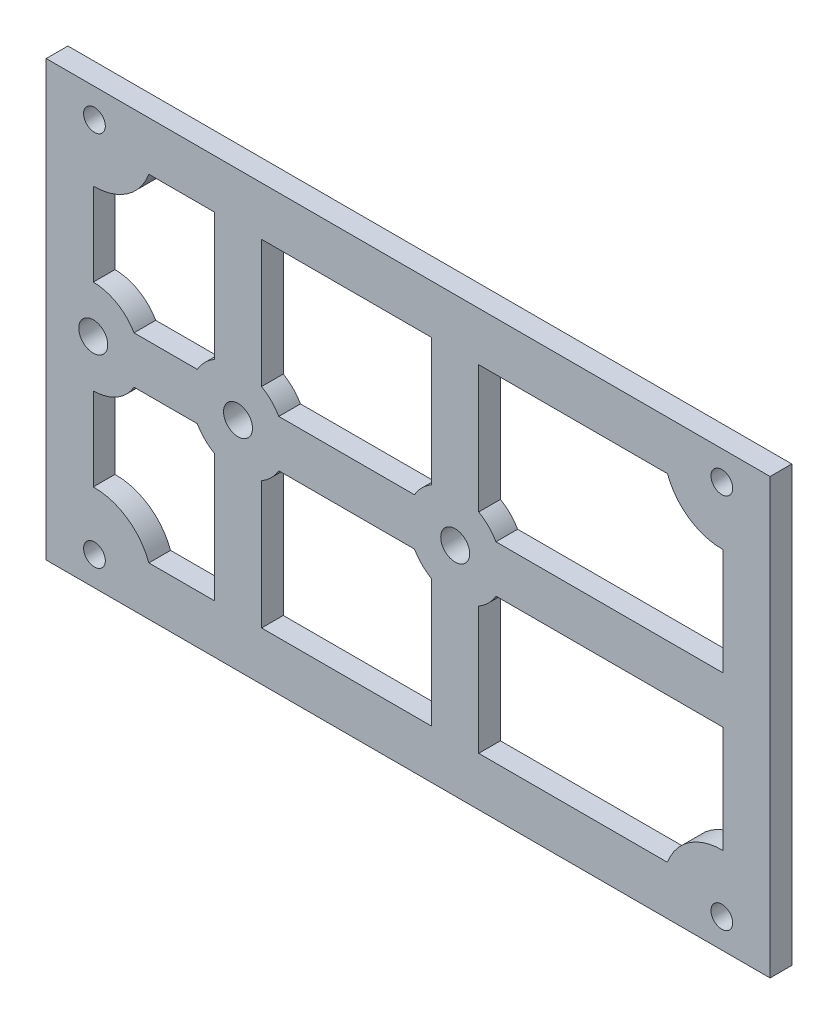
SolidWorks part; units mm, degrees
ref_plane "Front Plane" through (0, 0, 0) normal (0, 0, 1) x (1, 0, 0)
ref_plane "Top Plane" through (0, 0, 0) normal (0, 1, 0) x (1, 0, 0)
ref_plane "Right Plane" through (0, 0, 0) normal (1, 0, 0) x (0, 0, -1)
sketch "Sketch1" plane through (0, 0, 0) normal (0, 0, 1) x (1, 0, 0)
  line L1 (50, -30) -> (-50, -30)
  line L2 (50, -30) -> (50, 30)
  line L3 (50, 30) -> (-50, 30)
  line L4 (-50, -30) -> (-50, 30)
  line L5 (50, -30) -> (-50, 30) construction
  line L6 (50, 30) -> (-50, -30) construction
  point P0 (0, 0)
  dimension "D1" = 100
  dimension "D2" = 60
extrude "Boss-Extrude1" add sketch "Sketch1" along normal blind 3
sketch "Sketch3" plane through (0, 0, 0) normal (0, 0, -1) x (-1, 0, 0)
  line L0 (50, 0) -> (-6.5, 0) construction
  line L1 (50, 30) -> (50, -30) construction
  line L2 (50, -30) -> (50, 30) construction
  line L3 (-50, 30) -> (50, 30) construction
  line L4 (29.1292, 3.25) -> (37.8708, 3.25)
  line L5 (26.75, 5.6292) -> (26.75, 23.25)
  line L6 (26.75, 23.25) -> (35.8208, 23.25)
  line L7 (43.5, 6.5) -> (43.5, 18.0017)
  line L8 (-9.75, 23.25) -> (-35.8208, 23.25)
  line L9 (-9.75, 23.25) -> (-9.75, 5.6292)
  line L10 (-12.1292, 3.25) -> (-43.5, 3.25)
  line L11 (-43.5, 18.0017) -> (-43.5, 3.25)
  line L16 (-50, -30) -> (-50, 30) construction
  line L17 (-50, -30) -> (50, 30) construction
  line L18 (-50, 30) -> (50, -30) construction
  line L19 (-6.5, 0) -> (-50, 0) construction
  line L20 (-0.8708, 3.25) -> (17.8708, 3.25)
  line L21 (-3.25, 5.6292) -> (-3.25, 23.25)
  line L22 (-3.25, 23.25) -> (20.25, 23.25)
  line L23 (20.25, 5.6292) -> (20.25, 23.25)
  circle A1 centre (43.3333, 26) radius 1.5
  circle A2 centre (-43.3333, 26) radius 1.5
  circle A3 centre (23.5, 0) radius 2
  circle A4 centre (-6.5, 0) radius 2
  arc A6 (-43.5, 18.0017) -> (-35.8208, 23.25) centre (-43.3333, 26) ccw
  arc A7 (35.8208, 23.25) -> (43.5, 18.0017) centre (43.3333, 26) ccw
  arc A8 (-0.8708, 3.25) -> (-3.25, 5.6292) centre (-6.5, 0) ccw
  arc A9 (29.1292, 3.25) -> (26.75, 5.6292) centre (23.5, 0) ccw
  arc A10 (-9.75, 5.6292) -> (-12.1292, 3.25) centre (-6.5, 0) ccw
  arc A11 (43.5, 6.5) -> (37.8708, 3.25) centre (43.5, 0) ccw
  arc A12 (20.25, 5.6292) -> (17.8708, 3.25) centre (23.5, 0) ccw
  circle A13 centre (43.5, 0) radius 2
  dimension "D3" = 6.5
  dimension "D13" = 4
  dimension "D14" = 4
  dimension "D15" = 3
  dimension "D16" = 3
  dimension "D17" = 6.5
  dimension "D18" = 6.5
  dimension "D19" = 6.5
  dimension "D21" = 6.5
  dimension "D4" = 30
  dimension "D5" = 20
  dimension "D6" = 6.5
  dimension "D7" = 6.5
  dimension "D8" = 3.25
  dimension "D9" = 3.25
  dimension "D10" = 6.5
  dimension "D11" = 20
  dimension "D12" = 20
  dimension "D20" = 20
  dimension "D22" = 6.5
  dimension "D23" = 4
  dimension "D24" = 4
ref_plane "Plane1" through (50, -30, 0) normal (0, 1, 0) x (1, 0, 0)
sketch "Sketch4" plane through (0, 0, 0) normal (0, 0, 1) x (1, 0, 0)
extrude "Cut-Extrude2" cut sketch "Sketch3" against normal blind 10 contours A10 L9 L8 A6 L11 L10 | A9 L23 L22 L21 A8 L20 | A4 | A3 | A11 L7 A7 L6 L5 A9 L4 | A1 | A2 | A13 region at (-34.3924, 12.9447, 0) region at (26.0723, 12.9374, 0) region at (-8.5, 13.3813, 0) region at (-43.3333, 26, 0) region at (-23.5, 0, 0) region at (6.5, 0, 0)
mirror "Mirror3" about plane through (0, 0, 0) normal (0, 1, 0) of "Cut-Extrude2"
